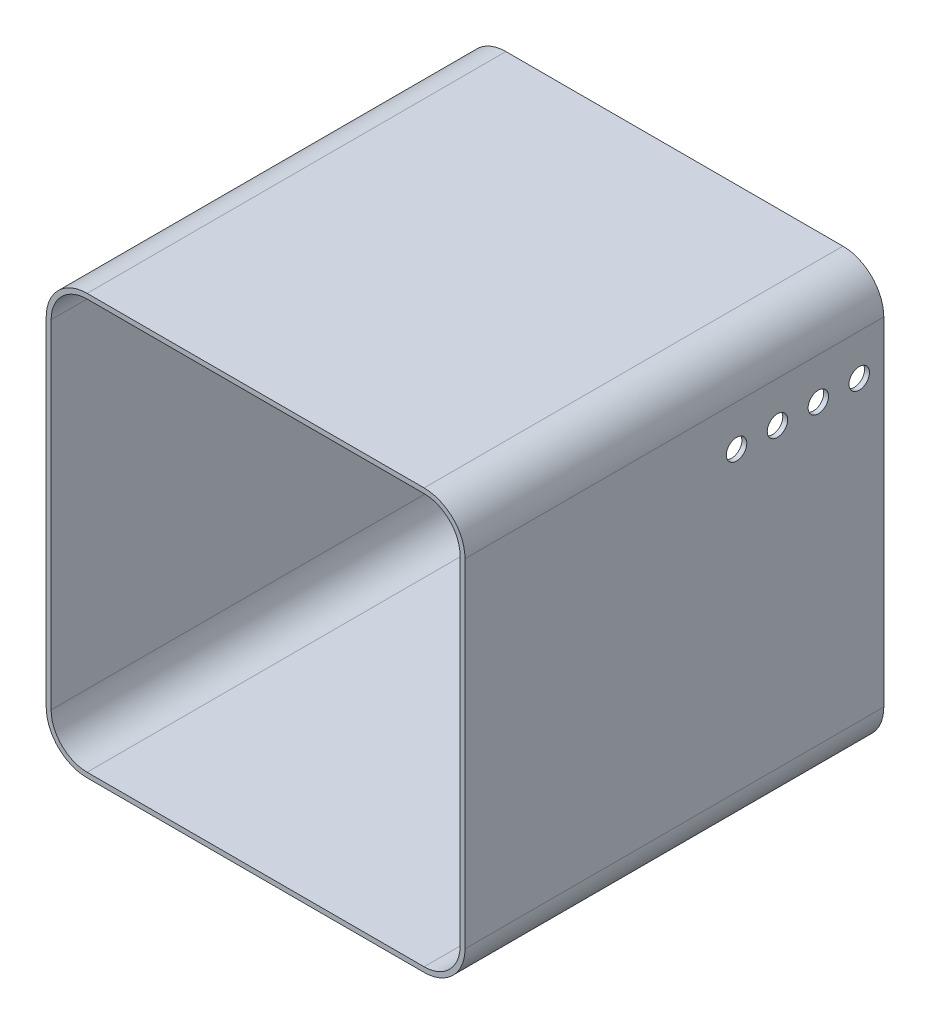
SolidWorks part; units mm, degrees
material "Pine"
ref_plane "Front Plane" through (0, 0, 0) normal (0, 0, 1) x (1, 0, 0)
ref_plane "Top Plane" through (0, 0, 0) normal (0, 1, 0) x (1, 0, 0)
ref_plane "Right Plane" through (0, 0, 0) normal (1, 0, 0) x (0, 0, -1)
sketch "Sketch1" plane through (0, 0, 0) normal (0, 0, 1) x (1, 0, 0)
  line L1 (44, 0) -> (456, 0)
  line L2 (0, 44) -> (0, 457)
  line L3 (44, 501) -> (456, 501)
  line L4 (500, 44) -> (500, 457)
  arc A0 (0, 457) -> (44, 501) centre (44, 457) cw
  arc A1 (456, 501) -> (500, 457) centre (456, 457) cw
  arc A2 (456, 0) -> (500, 44) centre (456, 44) ccw
  arc A3 (44, 0) -> (0, 44) centre (44, 44) cw
  point P9 (0, 501)
  point P12 (500, 501)
  point P15 (500, 0)
  point P18 (0, 0)
  dimension "D3" = 44
  dimension "D4" = 44
  dimension "D5" = 44
  dimension "D6" = 44
  dimension "D1" = 500
  dimension "D2" = 501
extrude "Extrude-Thin1" add sketch "Sketch1" against normal blind 512 thin contours A0 L3 A1 L4 A2 L1 A3 L2 thin type one direction wall 6
sketch "Sketch2" plane through (0, 0, 0) normal (1, 0, 0) x (0, 0, -1)
  line L0 (0, 322) -> (512, 322)
  line L1 (0, 44) -> (0, 457) construction
  line L2 (512, 457) -> (0, 457) construction
  dimension "D1" = 135
  dimension "D2" = 512
sketch "Sketch3" plane through (506, 0, 0) normal (1, 0, 0) x (0, 0, -1)
  line L0 (512, 44) -> (512, 457) construction
  line L1 (512, 457) -> (0, 457) construction
  circle A0 centre (482, 407) radius 12.5
  dimension "D1" = 30
  dimension "D2" = 25
  dimension "D3" = 50
extrude "Cut-Extrude1" cut sketch "Sketch3" against normal blind 10
pattern_linear "LPattern1" count 4 spacing 50 along (0, 0, 1) of "Cut-Extrude1"
